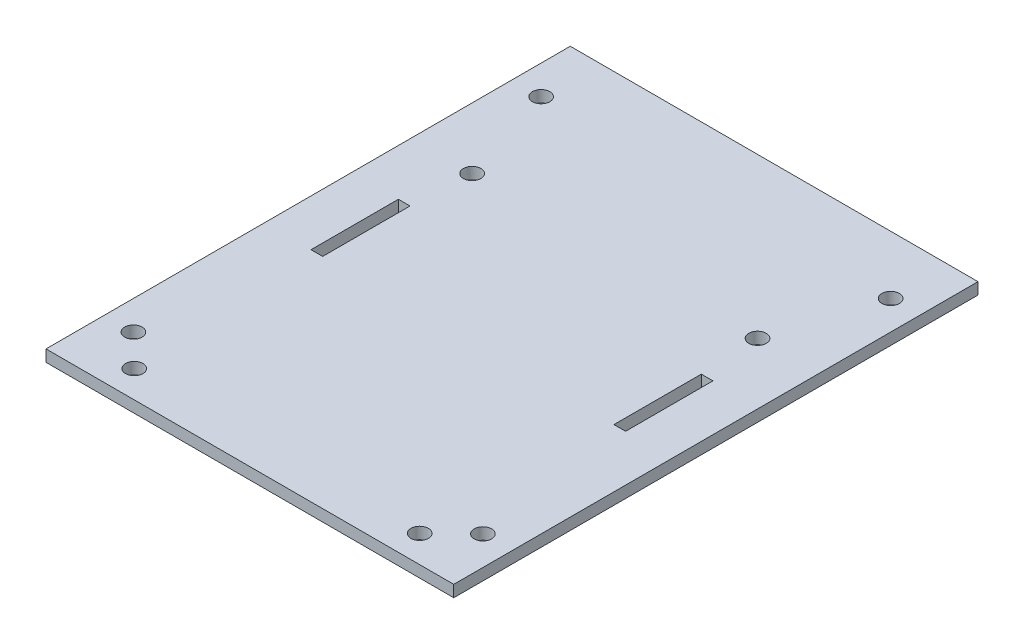
SolidWorks part; units mm, degrees
ref_plane "前基準面" through (0, 0, 0) normal (0, 0, 1) x (1, 0, 0)
ref_plane "上基準面" through (0, 0, 0) normal (0, 1, 0) x (1, 0, 0)
ref_plane "右基準面" through (0, 0, 0) normal (1, 0, 0) x (0, 0, -1)
sketch "草圖1" plane through (0, 0, 0) normal (0, 1, 0) x (1, 0, 0)
  line L0 (27, 0) -> (25, 0) construction
  line L1 (-35, -45) -> (35, -45)
  line L2 (-35, -45) -> (-35, 45)
  line L3 (-35, 45) -> (35, 45)
  line L4 (35, -45) -> (35, 45)
  line L5 (0, 45) -> (0, -45) construction
  line L6 (-35, 0) -> (35, 0) construction
  line L7 (-28, -42.5) -> (28, -42.5) construction
  line L8 (-28, -42.5) -> (-28, 42.5) construction
  line L9 (-28, 42.5) -> (28, 42.5) construction
  line L10 (28, -42.5) -> (28, 42.5) construction
  line L11 (0, 42.5) -> (0, -42.5) construction
  line L12 (-28, 0) -> (28, 0) construction
  line L13 (-27, -7.5) -> (-25, -7.5)
  line L14 (-27, -7.5) -> (-27, 7.5)
  line L15 (-27, 7.5) -> (-25, 7.5)
  line L16 (-25, -7.5) -> (-25, 7.5)
  line L17 (-26, 7.5) -> (-26, -7.5) construction
  line L18 (-27, 0) -> (-25, 0) construction
  line L19 (26, 7.5) -> (26, -7.5) construction
  line L20 (25, -7.5) -> (25, 7.5)
  line L21 (27, 7.5) -> (25, 7.5)
  line L22 (27, -7.5) -> (27, 7.5)
  line L23 (27, -7.5) -> (25, -7.5)
  circle A0 centre (-30, 35) radius 1.5
  circle A1 centre (30, 35) radius 1.5
  circle A2 centre (30, -35) radius 1.5
  circle A3 centre (-30, -35) radius 1.5
  circle A4 centre (24.5, 17.65) radius 1.5
  circle A5 centre (24.5, -40.35) radius 1.5
  circle A6 centre (-24.5, 17.65) radius 1.5
  circle A7 centre (-24.5, -40.35) radius 1.5
  point P0 (0, 0)
  point P15 (0, 0)
  point P26 (-26, 0)
  point P42 (26, 0)
  point P43 (-26.7502, -4.8933)
  dimension "D1" = 3
  dimension "D6" = 24.85
  dimension "D7" = 3
  dimension "D2" = 70
  dimension "D3" = 60
  dimension "D4" = 85
  dimension "D5" = 56
  dimension "D8" = 49
  dimension "D9" = 58
  dimension "D10" = 90
  dimension "D11" = 70
  dimension "D12" = 50
  dimension "D13" = 15
  dimension "D14" = 2
extrude "填料-伸長1" add sketch "草圖1" along normal blind 2
